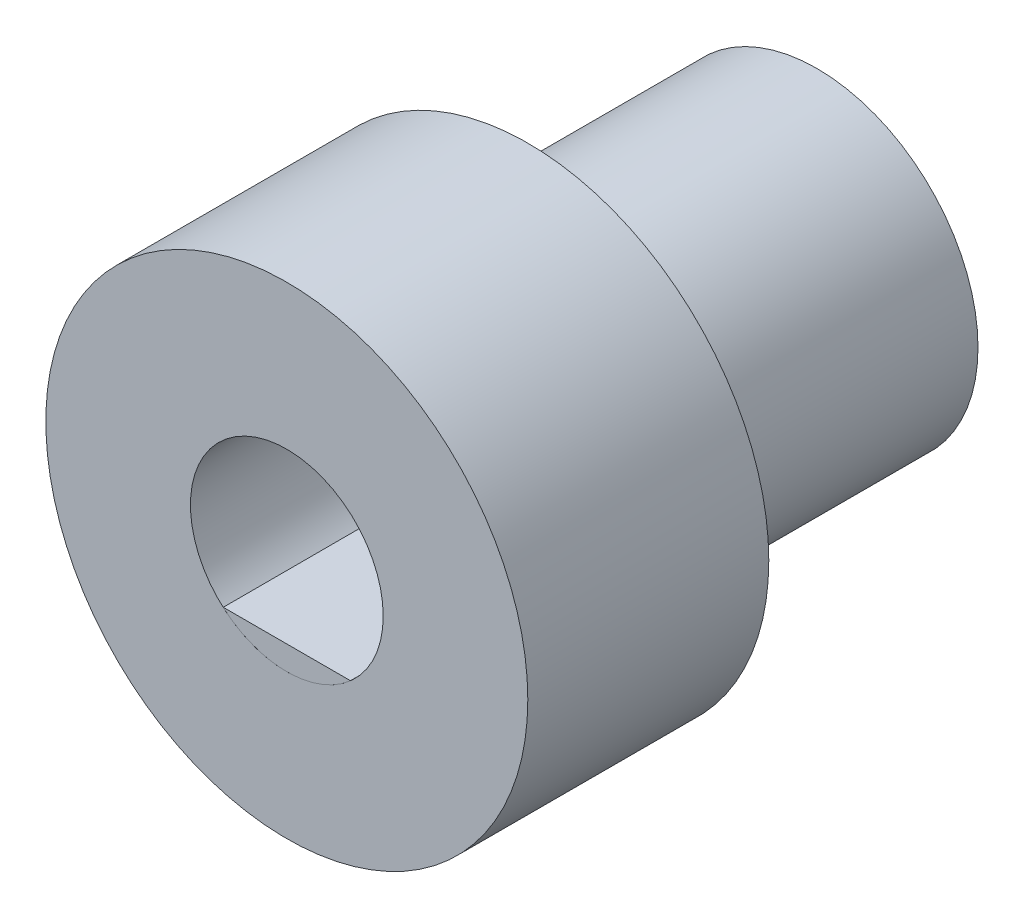
SolidWorks part; units mm, degrees
ref_plane "Plan de face" through (0, 0, 0) normal (0, 0, 1) x (1, 0, 0)
ref_plane "Plan de dessus" through (0, 0, 0) normal (0, 1, 0) x (1, 0, 0)
ref_plane "Plan de droite" through (0, 0, 0) normal (1, 0, 0) x (0, 0, -1)
sketch "Esquisse1" plane through (0, 0, 0) normal (0, 0, 1) x (1, 0, 0)
  circle A0 centre (0, 0) radius 10
  dimension "D1" = 20
extrude "Boss.-Extru.1" add sketch "Esquisse1" along normal blind 10
sketch "Esquisse2" plane through (0, 0, 0) normal (0, 0, -1) x (-1, 0, 0)
  circle A0 centre (0, 0) radius 6.6805
extrude "Boss.-Extru.2" add sketch "Esquisse2" along normal blind 12 separate body
sketch "Esquisse3" plane through (0, 0, 10) normal (0, 0, 1) x (1, 0, 0)
  circle A0 centre (0, 0) radius 4
  dimension "D1" = 8
extrude "Enlèv. mat.-Extru.1" cut sketch "Esquisse3" against normal up to next (10 mm away)
sketch "Esquisse4" plane through (0, 0, -12) normal (0, 0, -1) x (-1, 0, 0)
  circle A0 centre (0, 0) radius 2
  dimension "D1" = 4
extrude "Enlèv. mat.-Extru.2" cut sketch "Esquisse4" against normal up to next (12 mm away)
sketch "Esquisse5" plane through (0, 0, 10) normal (0, 0, 1) x (1, 0, 0)
  line L0 (-2.6458, -3) -> (2.6458, -3)
  arc A0 (-2.6458, -3) -> (2.6458, -3) centre (0, 0) ccw
  circle A1 centre (0, 0) radius 4 construction
  dimension "D1" = 3
extrude "Boss.-Extru.3" add sketch "Esquisse5" against normal up to next separate body
sketch "Esquisse6" plane through (0, 0, -12) normal (0, 0, -1) x (-1, 0, 0)
  line L0 (-1.7321, -1) -> (1.7321, -1)
  arc A0 (1.7321, -1) -> (-1.7321, -1) centre (0, 0) cw
  circle A1 centre (0, 0) radius 2 construction
  dimension "D1" = 1
extrude "Boss.-Extru.4" add sketch "Esquisse6" against normal up to surface (12 mm away) up to face at (4, 0, 0)
